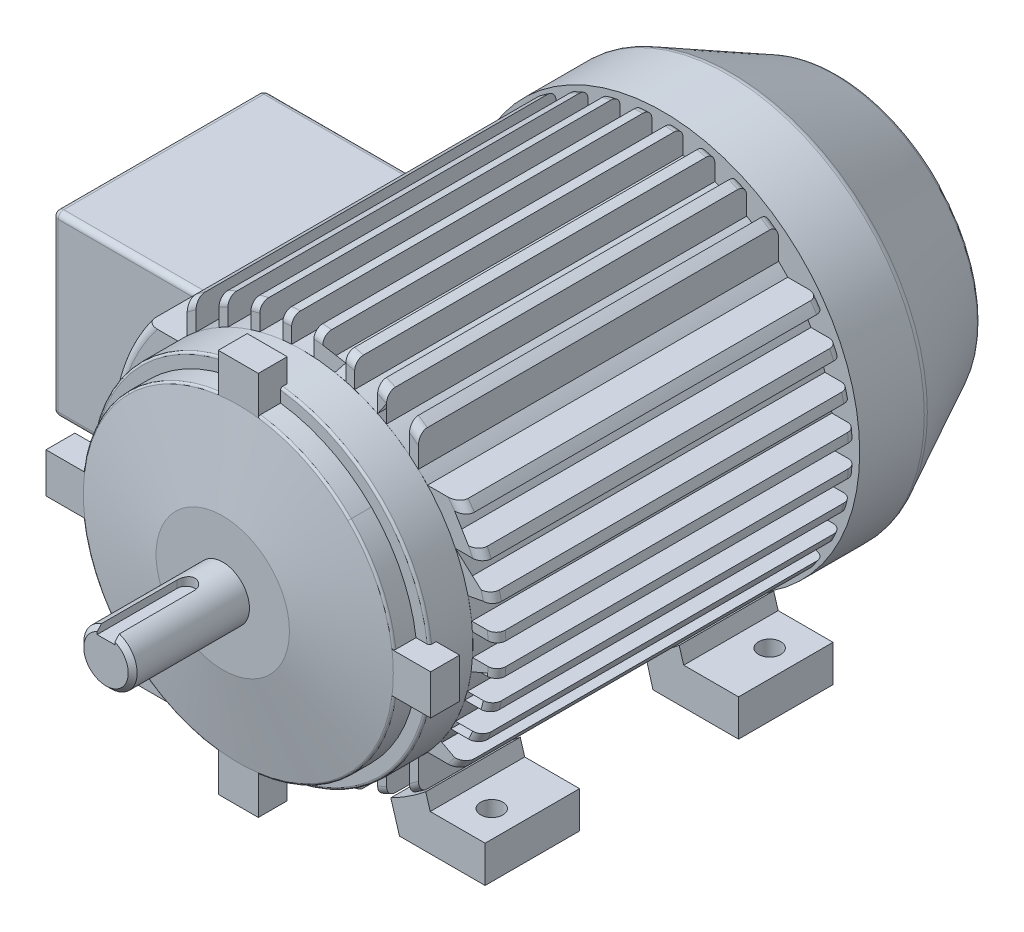
SolidWorks part; units mm, degrees
ref_plane "Alzado" through (0, 0, 0) normal (0, 0, 1) x (1, 0, 0)
ref_plane "Planta" through (0, 0, 0) normal (0, 1, 0) x (1, 0, 0)
ref_plane "Vista lateral" through (0, 0, 0) normal (1, 0, 0) x (0, 0, -1)
sketch "Croquis1" plane through (0, 0, 0) normal (0, 0, 1) x (1, 0, 0)
  line L0 (-4.999, 76.3364) -> (-4.999, 87.357)
  line L1 (9.001, 75.9687) -> (9.001, 87.0359)
  line L2 (0.001, 0) -> (-138.1695, 0) construction
  line L3 (48.001, -59.5672) -> (48.001, -73.1591)
  line L4 (75.9697, -9) -> (87.0369, -9)
  line L5 (76.3374, 5) -> (87.358, 5)
  line L6 (52.001, -56.1093) -> (52.001, -70.3722)
  line L7 (37.668, -66.5841) -> (37.668, -78.9775)
  line L8 (-51.999, 56.1093) -> (-51.999, 70.3722)
  line L9 (48.001, 59.5672) -> (48.001, 73.1591)
  line L10 (-37.666, 66.5841) -> (-37.666, 78.9775)
  line L11 (-23.333, 72.8545) -> (-23.333, 84.3313)
  line L12 (19.335, 74.0165) -> (19.335, 85.3373)
  line L13 (37.668, 66.5841) -> (37.668, 78.9775)
  line L14 (33.668, -68.6934) -> (33.668, -80.7637)
  line L15 (23.335, -72.8545) -> (23.335, -84.3313)
  line L16 (19.335, -74.0165) -> (19.335, -85.3373)
  line L17 (5.001, -76.3364) -> (5.001, -87.357)
  line L18 (9.001, -75.9687) -> (9.001, -87.0359)
  line L19 (-4.999, -76.3364) -> (-4.999, -87.357)
  line L20 (66.5851, 37.667) -> (78.9785, 37.667)
  line L21 (72.8555, 23.334) -> (84.3323, 23.334)
  line L22 (56.1103, 52) -> (70.3732, 52)
  line L23 (68.6944, -33.667) -> (80.7647, -33.667)
  line L24 (74.0175, -19.334) -> (85.3383, -19.334)
  line L25 (56.1103, -52) -> (70.3732, -52)
  line L26 (-56.1083, 52) -> (-70.3712, 52)
  line L27 (-56.1083, -52) -> (-70.3712, -52)
  line L28 (59.5682, 48) -> (73.1601, 48)
  line L29 (68.6944, 33.667) -> (80.7647, 33.667)
  line L30 (74.0175, 19.334) -> (85.3383, 19.334)
  line L31 (72.8555, -23.334) -> (84.3323, -23.334)
  line L32 (66.5851, -37.667) -> (78.9785, -37.667)
  line L33 (59.5682, -48) -> (73.1601, -48)
  line L34 (-47.999, 59.5672) -> (-47.999, 73.1591)
  line L35 (-33.666, 68.6934) -> (-33.666, 80.7637)
  line L36 (-19.333, 74.0165) -> (-19.333, 85.3373)
  line L37 (23.335, 72.8545) -> (23.335, 84.3313)
  line L38 (33.668, 68.6934) -> (33.668, 80.7637)
  line L39 (52.001, 56.1093) -> (52.001, 70.3722)
  line L40 (-8.999, -75.9687) -> (-8.999, -87.0359)
  line L41 (-19.333, -74.0165) -> (-19.333, -85.3373)
  line L42 (-23.333, -72.8545) -> (-23.333, -84.3313)
  line L43 (-37.666, -66.5841) -> (-37.666, -78.9775)
  line L44 (-33.666, -68.6934) -> (-33.666, -80.7637)
  line L45 (-47.999, -59.5672) -> (-47.999, -73.1591)
  line L46 (-51.999, -56.1093) -> (-51.999, -70.3722)
  line L48 (5.001, 76.3364) -> (5.001, 87.357)
  line L49 (-8.999, 75.9687) -> (-8.999, 87.0359)
  line L50 (75.9697, 9) -> (87.0369, 9)
  line L51 (76.3374, -5) -> (87.358, -5)
  arc A0 (-56.1083, -52) -> (-51.999, -56.1093) centre (0.001, 0) ccw
  arc A1 (-70.3712, 52) -> (-70.3712, -52) centre (0.001, 0) ccw
  arc A3 (-47.999, 73.1591) -> (-51.999, 70.3722) centre (0.001, 0) ccw
  arc A4 (-33.666, 80.7637) -> (-37.666, 78.9775) centre (0.001, 0) ccw
  arc A5 (-19.333, 85.3373) -> (-23.333, 84.3313) centre (0.001, 0) ccw
  arc A6 (-4.999, 87.357) -> (-8.999, 87.0359) centre (0.001, 0) ccw
  arc A7 (9.001, 87.0359) -> (5.001, 87.357) centre (0.001, 0) ccw
  arc A8 (23.335, 84.3313) -> (19.335, 85.3373) centre (0.001, 0) ccw
  arc A9 (37.668, 78.9775) -> (33.668, 80.7637) centre (0.001, 0) ccw
  arc A10 (52.001, 70.3722) -> (48.001, 73.1591) centre (0.001, 0) ccw
  arc A11 (73.1601, 48) -> (70.3732, 52) centre (0.001, 0) ccw
  arc A12 (80.7647, 33.667) -> (78.9785, 37.667) centre (0.001, 0) ccw
  arc A13 (85.3383, 19.334) -> (84.3323, 23.334) centre (0.001, 0) ccw
  arc A14 (87.358, 5) -> (87.0369, 9) centre (0.001, 0) ccw
  arc A15 (87.0369, -9) -> (87.358, -5) centre (0.001, 0) ccw
  arc A16 (84.3323, -23.334) -> (85.3383, -19.334) centre (0.001, 0) ccw
  arc A17 (78.9785, -37.667) -> (80.7647, -33.667) centre (0.001, 0) ccw
  arc A18 (70.3732, -52) -> (73.1601, -48) centre (0.001, 0) ccw
  arc A19 (52.001, -70.3722) -> (48.001, -73.1591) centre (0.001, 0) cw
  arc A20 (37.668, -78.9775) -> (33.668, -80.7637) centre (0.001, 0) cw
  arc A21 (23.335, -84.3313) -> (19.335, -85.3373) centre (0.001, 0) cw
  arc A22 (9.001, -87.0359) -> (5.001, -87.357) centre (0.001, 0) cw
  arc A23 (-4.999, -87.357) -> (-8.999, -87.0359) centre (0.001, 0) cw
  arc A24 (-19.333, -85.3373) -> (-23.333, -84.3313) centre (0.001, 0) cw
  arc A25 (-33.666, -80.7637) -> (-37.666, -78.9775) centre (0.001, 0) cw
  arc A26 (-47.999, -73.1591) -> (-51.999, -70.3722) centre (0.001, 0) cw
  arc A27 (-51.999, 56.1093) -> (-56.1083, 52) centre (0.001, 0) ccw
  arc A28 (-37.666, 66.5841) -> (-47.999, 59.5672) centre (0.001, 0) ccw
  arc A29 (-23.333, 72.8545) -> (-33.666, 68.6934) centre (0.001, 0) ccw
  arc A30 (-8.999, 75.9687) -> (-19.333, 74.0165) centre (0.001, 0) ccw
  arc A31 (5.001, 76.3364) -> (-4.999, 76.3364) centre (0.001, 0) ccw
  arc A32 (19.335, 74.0165) -> (9.001, 75.9687) centre (0.001, 0) ccw
  arc A33 (33.668, 68.6934) -> (23.335, 72.8545) centre (0.001, 0) ccw
  arc A34 (48.001, 59.5672) -> (37.668, 66.5841) centre (0.001, 0) ccw
  arc A35 (56.1103, 52) -> (52.001, 56.1093) centre (0.001, 0) ccw
  arc A36 (66.5851, 37.667) -> (59.5682, 48) centre (0.001, 0) ccw
  arc A37 (72.8555, 23.334) -> (68.6944, 33.667) centre (0.001, 0) ccw
  arc A38 (75.9697, 9) -> (74.0175, 19.334) centre (0.001, 0) ccw
  arc A39 (59.5682, -48) -> (66.5851, -37.667) centre (0.001, 0) ccw
  arc A40 (68.6944, -33.667) -> (72.8555, -23.334) centre (0.001, 0) ccw
  arc A41 (74.0175, -19.334) -> (75.9697, -9) centre (0.001, 0) ccw
  arc A42 (76.3374, -5) -> (76.3374, 5) centre (0.001, 0) ccw
  arc A43 (52.001, -56.1093) -> (56.1103, -52) centre (0.001, 0) ccw
  arc A44 (37.668, -66.5841) -> (48.001, -59.5672) centre (0.001, 0) ccw
  arc A45 (23.335, -72.8545) -> (33.668, -68.6934) centre (0.001, 0) ccw
  arc A46 (9.001, -75.9687) -> (19.335, -74.0165) centre (0.001, 0) ccw
  arc A47 (-4.999, -76.3364) -> (5.001, -76.3364) centre (0.001, 0) ccw
  arc A48 (-19.333, -74.0165) -> (-8.999, -75.9687) centre (0.001, 0) ccw
  arc A49 (-33.666, -68.6934) -> (-23.333, -72.8545) centre (0.001, 0) ccw
  arc A50 (-47.999, -59.5672) -> (-37.666, -66.5841) centre (0.001, 0) ccw
  dimension "D2" = 87.5
  dimension "D5" = 87.5
  dimension "D6" = 87.5
  dimension "D7" = 87.5
  dimension "D8" = 87.5
  dimension "D9" = 87.5
  dimension "D10" = 87.5
  dimension "D11" = 87.5
  dimension "D26" = 87.5
  dimension "D27" = 87.5
  dimension "D28" = 87.5
  dimension "D29" = 87.5
  dimension "D30" = 87.5
  dimension "D31" = 87.5
  dimension "D32" = 87.5
  dimension "D33" = 87.5
  dimension "D51" = 87.5
  dimension "D1" = 104
  dimension "D3" = 4
  dimension "D4" = 10.333
  dimension "D12" = 104
  dimension "D13" = 52
  dimension "D14" = 4
  dimension "D15" = 10.333
  dimension "D16" = 4
  dimension "D17" = 10.334
  dimension "D18" = 4
  dimension "D19" = 10
  dimension "D20" = 18
  dimension "D21" = 10.334
  dimension "D22" = 4
  dimension "D23" = 18.333
  dimension "D24" = 4
  dimension "D25" = 10.333
  dimension "D34" = 52
  dimension "D35" = 104
  dimension "D36" = 4
  dimension "D37" = 18.333
  dimension "D38" = 14.333
  dimension "D39" = 4
  dimension "D40" = 4
  dimension "D41" = 4
  dimension "D42" = 10.334
  dimension "D43" = 14
  dimension "D44" = 4
  dimension "D45" = 14.334
  dimension "D46" = 4
  dimension "D47" = 4
  dimension "D48" = 14.333
  dimension "D49" = 10.333
  dimension "D50" = 52
  dimension "D52" = 0.001
  dimension "D53" = 0.001
extrude "Extruir1" add sketch "Croquis1" against normal blind 162
fillet "Redondeo1" radius 4 50 edges at (-50.0184, -71.7935, -162) (-35.6772, -79.8957, -162) (-21.3389, -84.8579, -162) (-7.0008, -87.2194, -162) (7.0028, -87.2194, -162) (21.3409, -84.8579, -162) (35.6792, -79.8957, -162) (50.0204, -71.7935, -162) (71.7945, -50.0194, -162) (79.8967, -35.6782, -162) (84.8589, -21.3399, -162) (87.2204, -7.0018, -162) (87.2204, 7.0018, -162) (84.8589, 21.3399, -162) (79.8967, 35.6782, -162) (71.7945, 50.0194, -162) (50.0204, 71.7935, -162) (35.6792, 79.8957, -162) (21.3409, 84.8579, -162) (7.0028, 87.2194, -162) (-7.0008, 87.2194, -162) (-21.3389, 84.8579, -162) (-35.6772, 79.8957, -162) (-50.0184, 71.7935, -162) (-87.499, 0, -162) (-87.499, 0, 0) (-7.0008, -87.2194, 0) (-21.3389, -84.8579, 0) (-35.6772, -79.8957, 0) (-50.0184, -71.7935, 0) (7.0028, -87.2194, 0) (21.3409, -84.8579, 0) (35.6792, -79.8957, 0) (50.0204, -71.7935, 0) (71.7945, -50.0194, 0) (79.8967, -35.6782, 0) (84.8589, -21.3399, 0) (87.2204, -7.0018, 0) (87.2204, 7.0018, 0) (84.8589, 21.3399, 0) (79.8967, 35.6782, 0) (71.7945, 50.0194, 0) (50.0204, 71.7935, 0) (35.6792, 79.8957, 0) (21.3409, 84.8579, 0) (7.0028, 87.2194, 0) (-7.0008, 87.2194, 0) (-21.3389, 84.8579, 0) (-35.6772, 79.8957, 0) (-50.0184, 71.7935, 0)
sketch "Croquis2" plane through (0, 0, 0) normal (0, 0, 1) x (1, 0, 0)
  circle A0 centre (0, 0) radius 76.5
  dimension "D1" = 153
extrude "Extruir2" add sketch "Croquis2" along normal blind 19
sketch "Croquis3" plane through (0, 0, 19) normal (0, 0, 1) x (1, 0, 0)
  circle A0 centre (0, 0) radius 70.5
  dimension "D1" = 141
extrude "Extruir3" add sketch "Croquis3" along normal blind 10
sketch "Croquis4" plane through (0, 0, 29) normal (0, 0, 1) x (1, 0, 0)
  circle A0 centre (0, 0) radius 12
  dimension "D1" = 24
extrude "Extruir4" add sketch "Croquis4" along normal blind 59.5
ref_plane "Plano1" through (0, 12, 0) normal (0, 1, 0) x (-1, 0, 0)
sketch "Croquis5" plane through (0, 12, 0) normal (0, 1, 0) x (-1, 0, 0)
  line L1 (-4.0005, 88.5) -> (3.9995, 88.5)
  line L2 (-4.0005, 88.5) -> (-4.0005, 52.5)
  line L4 (3.9995, 88.5) -> (3.9995, 52.5)
  line L6 (12, 88.5) -> (-12, 88.5) construction
  arc A0 (-4.0005, 52.5) -> (3.9995, 52.5) centre (-0.0005, 52.5) ccw
  dimension "D4" = 36
  dimension "D3" = 4
  dimension "D1" = 4
  dimension "D2" = 8
  dimension "D5" = 36
extrude "Cortar-Extruir1" cut sketch "Croquis5" against normal blind 4
chamfer "Chaflán1" distance 2 angle 45 1 edges at (-0.0005, -12, 88.5)
sketch "Croquis7" plane through (0, 0, -162) normal (0, 0, -1) x (-1, 0, 0)
  circle A0 centre (0, 0) radius 88.5
  dimension "D1" = 177
extrude "Extruir5" add sketch "Croquis7" along normal blind 79
chamfer "Chaflán2" distance 49 distance2 25 1 edges at (-88.5, 0, -241) first distance on face at (-88.5, 0, -241)
fillet "Redondeo2" radius 4 2 edges at (-88.5, 0, -192) (-63.5, 0, -241)
sketch "Croquis8" plane through (0, 0, 29) normal (0, 0, 1) x (1, 0, 0)
  line L1 (-9, 86.5) -> (9, 86.5)
  line L2 (-9, 86.5) -> (-9, 69.9232)
  line L4 (9, 86.5) -> (9, 69.9232)
  arc A0 (9, 69.9232) -> (-9, 69.9232) centre (0, 0) ccw
  dimension "D1" = 141
  dimension "D2" = 9
  dimension "D3" = 18
  dimension "D4" = 86.5
extrude "Extruir6" add sketch "Croquis8" against normal blind 13
pattern_circular "MatrizC1" count 4 over 360 about axis through (0.001, 0, -162) along (0, 0, 1) of "Extruir3", "Extruir6"
sketch "Croquis9" plane through (0, 0, 0) normal (0, 0, 1) x (1, 0, 0)
  line L0 (-82, -91) -> (-43.5, -91)
  line L1 (-82, -91) -> (-82, -74.5)
  line L2 (-82, -74.5) -> (-57.325, -74.5)
  line L3 (82, -74.5) -> (82, -91)
  line L4 (43.5, -91) -> (82, -91)
  line L5 (82, -74.5) -> (57.325, -74.5)
  line L6 (-39.5895, -78.0315) -> (-43.5, -91)
  line L7 (0, 0) -> (0, -155.2671) construction
  line L8 (-57.325, -74.5) -> (-55.3061, -67.8047)
  line L9 (57.325, -74.5) -> (55.3061, -67.8047)
  line L10 (39.5895, -78.0315) -> (43.5, -91)
  arc A0 (-55.3061, -67.8047) -> (-39.5895, -78.0315) centre (0, 0) ccw
  arc A1 (39.5895, -78.0315) -> (55.3061, -67.8047) centre (0, 0) ccw
  dimension "D5" = 175
  dimension "D6" = 24.675
  dimension "D1" = 43.5
  dimension "D3" = 91
  dimension "D4" = 24.675
  dimension "D7" = 16.5
extrude "Extruir8" add sketch "Croquis9" against normal blind 42.5
ref_plane "Plano2" through (0, 0, -114) normal (0, 0, 1) x (1, 0, 0)
sketch "Croquis10" plane through (0, 0, -114) normal (0, 0, 1) x (1, 0, 0)
  line L0 (43.5, -91) -> (82, -91)
  line L1 (82, -91) -> (82, -74.5)
  line L2 (82, -74.5) -> (57.325, -74.5)
  line L3 (57.325, -74.5) -> (55.3061, -67.8047)
  line L4 (43.5, -91) -> (39.8244, -77.9119)
  line L5 (-55.3061, -67.8047) -> (-57.325, -74.5)
  line L6 (-57.325, -74.5) -> (-82, -74.5)
  line L7 (-82, -74.5) -> (-82, -91)
  line L8 (-82, -91) -> (-43.5, -91)
  line L9 (-43.5, -91) -> (-39.5895, -78.0315)
  arc A0 (39.5895, -78.0315) -> (55.3061, -67.8047) centre (0, 0) ccw construction
  arc A1 (-55.3061, -67.8047) -> (-39.5895, -78.0315) centre (0, 0) ccw
  arc A2 (39.8244, -77.9119) -> (55.3061, -67.8047) centre (0, 0) ccw
extrude "Extruir9" add sketch "Croquis10" against normal blind 42.5
sketch "Croquis11" plane through (0, -91, 0) normal (0, -1, 0) x (1, 0, 0)
  line L0 (43.5, 0) -> (82, 0) construction
  line L1 (-82, 0) -> (-43.5, 0) construction
  circle A0 centre (-69.9995, -15) radius 5
  circle A1 centre (70.0005, -15) radius 5
  circle A2 centre (70.0005, -140) radius 5
  circle A3 centre (-69.9995, -140) radius 5
  dimension "D7" = 10
  dimension "D8" = 10
  dimension "D9" = 10
  dimension "D10" = 10
  dimension "D1" = 15
  dimension "D2" = 15
  dimension "D3" = 140
  dimension "D4" = 70
  dimension "D5" = 70
  dimension "D6" = 140
  dimension "D11" = 125
  dimension "D12" = 125
extrude "Cortar-Extruir2" cut sketch "Croquis11" against normal blind 18
fillet "Redondeo3" radius 1 8 edges at (63.2766, -31.0898, 29) (-31.0888, -63.2756, 29) (63.2762, 31.0907, 29) (31.0917, -63.2752, 29) (-63.2742, -31.0907, 29) (-63.2746, 31.0898, 29) (-31.0897, 63.2752, 29) (31.0908, 63.2756, 29)
fillet "Redondeo4" radius 1 4 edges at (-54.0926, -54.0947, 19) (-54.094, 54.0933, 19) (54.0947, -54.0926, 19) (54.0933, 54.094, 19)
ref_plane "Plano3" through (0, 0, -130) normal (0, 0, 1) x (1, 0, 0)
sketch "Croquis12" plane through (0, 0, -130) normal (0, 0, 1) x (1, 0, 0)
  line L0 (-77.8219, 40) -> (-147.5, 40)
  line L1 (-147.5, 40) -> (-147.5, -40)
  line L2 (-147.5, -40) -> (-77.8219, -40)
  arc A0 (-77.8219, 40) -> (-77.8219, -40) centre (0, 0) ccw
  dimension "D1" = 87.5
  dimension "D2" = 147.5
  dimension "D3" = 40
  dimension "D4" = 80
extrude "Extruir10" add sketch "Croquis12" along normal blind 95
fillet "Redondeo5" radius 2.5 8 edges at (-147.5, 40, -82.5) (-147.5, -40, -82.5) (-147.5, 0, -35) (-147.5, 0, -130) (-112.661, -40, -130) (-112.661, -40, -35) (-112.661, 40, -130) (-112.661, 40, -35)
ref_plane "Plano4" through (0, 0, 36) normal (0, 0, 1) x (1, 0, 0)
sketch "Croquis13" plane through (0, 0, 36) normal (0, 0, 1) x (1, 0, 0)
  circle A0 centre (0, 0) radius 30
  dimension "D1" = 60
extrude "Extruir11" add sketch "Croquis13" against normal blind 7 draft 80 draft outward yes
ref_plane "Plano5" through (0, 0, 0) normal (1, 0, 0) x (0, 0, -1)
